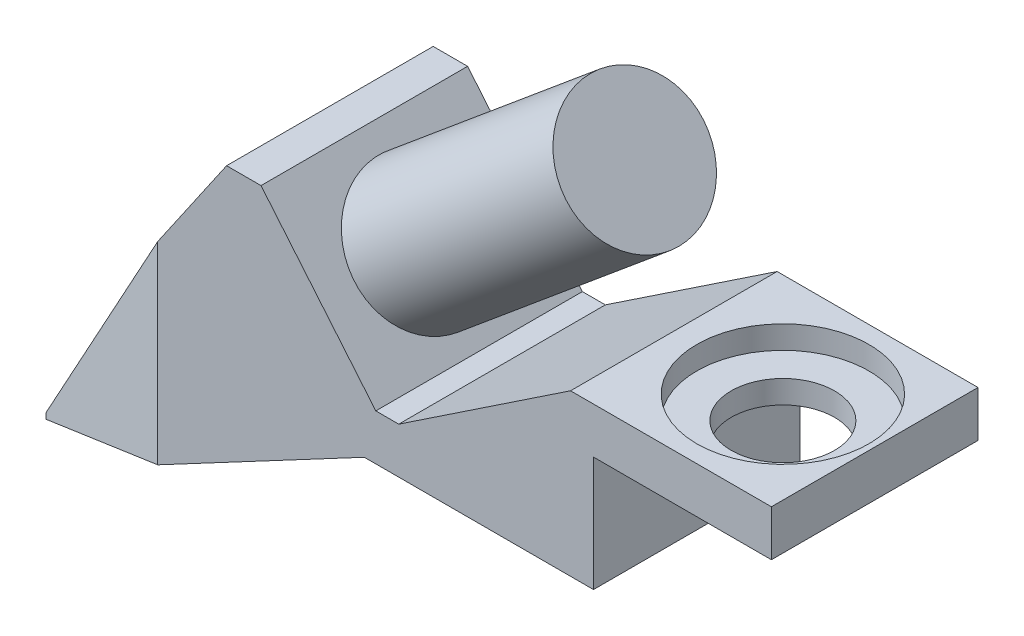
SolidWorks part; units mm, degrees
ref_plane "Front Plane" through (0, 0, 0) normal (0, 0, 1) x (1, 0, 0)
ref_plane "Top Plane" through (0, 0, 0) normal (0, 1, 0) x (1, 0, 0)
ref_plane "Right Plane" through (0, 0, 0) normal (1, 0, 0) x (0, 0, -1)
sketch "Sketch1" plane through (0, 0, 0) normal (0, 0, 1) x (1, 0, 0)
  line L0 (0, 0) -> (17.8667, 9.5)
  line L1 (17.8667, 9.5) -> (27.85, 9.5)
  line L2 (27.85, 9.5) -> (27.85, 14.5)
  line L3 (27.85, 14.5) -> (35.6, 14.5)
  line L4 (35.6, 14.5) -> (35.6, 16.5)
  line L5 (35.6, 16.5) -> (26.85, 16.5)
  line L8 (11.8667, 17.5) -> (0, 0.25)
  line L10 (18.3667, 11.5) -> (13.3667, 17.5)
  line L11 (13.3667, 17.5) -> (11.8667, 17.5)
  line L12 (26.85, 16.5) -> (19.3667, 11.5)
  line L13 (19.3667, 11.5) -> (18.3667, 11.5)
  line L14 (0, 0) -> (0, 0.25)
  dimension "D1" = 35.6
  dimension "D2" = 9.5
  dimension "D3" = 14.5
  dimension "D4" = 17.5
  dimension "D5" = 2
  dimension "D6" = 7.75
  dimension "D7" = 2
  dimension "D8" = 1.5
  dimension "D9" = 0.5
  dimension "D10" = 1
  dimension "D11" = 1
  dimension "D12" = 5
  dimension "D13" = 9
  dimension "D14" = 0.25
extrude "Boss-Extrude1" add sketch "Sketch1" along normal blind 9
sketch "Sketch2" plane through (0, 16.5, 0) normal (0, 1, 0) x (1, 0, 0)
  line L0 (35.6, -9) -> (35.6, 0) construction
  line L1 (8.8667, 0) -> (0, 0)
  line L2 (0, 0) -> (0, -4)
  line L3 (0, -4) -> (8.8667, 0)
  line L4 (0, -5) -> (0, -9)
  line L5 (0, -9) -> (8.8667, -9)
  line L6 (0, -9) -> (0, 0) construction
  line L7 (11.8667, 0) -> (0, 0) construction
  line L8 (0, -5) -> (8.8667, -9)
  line L9 (11.8667, -9) -> (0, -9) construction
  line L10 (11.8667, -9) -> (11.8667, 0) construction
  circle A0 centre (31.6, -4.5) radius 2.25
  circle A1 centre (31.6, -4.5) radius 3.75
  point P5 (35.6, -4.5)
  point P19 (0, -4.5)
  dimension "D3" = 4.5
  dimension "D5" = 7.5
  dimension "D1" = 4
  dimension "D2" = 1
  dimension "D4" = 3
  dimension "D6" = 0.5
extrude "Cut-Extrude1" cut sketch "Sketch2" against normal up to vertex (16.5 mm away) contours A0 | L2 L3 L1 | L8 L4 L5 region at (2.9556, 16.5, 1.3333) region at (2.9556, 16.5, 7.6667) region at (31.6, 16.5, 4.5) up to point (0, 0, 9)
extrude "Cut-Extrude2" cut sketch "Sketch2<3>" against normal blind 1 contours A1 A0 region at (27.9561, 16.5, 4.5)
sketch "Sketch2<3>" plane through (0, 16.5, 0) normal (0, 1, 0) x (1, 0, 0) same geometry as "Sketch2"
sketch "Sketch3" plane through (16.4951, 13.7459, 0) normal (0.7682, 0.6402, 0) x (0, 0, -1)
  line L0 (-9, 4.8867) -> (0, 4.8867) construction
  circle A0 centre (-4.5, 0.8867) radius 3
  point P4 (-4.5, 4.8867)
  dimension "D1" = 6
  dimension "D2" = 4
extrude "Boss-Extrude2" add sketch "Sketch3" along normal blind 12
equation "\"D6@Sketch2\"=\"D2@Sketch2\"/2"
